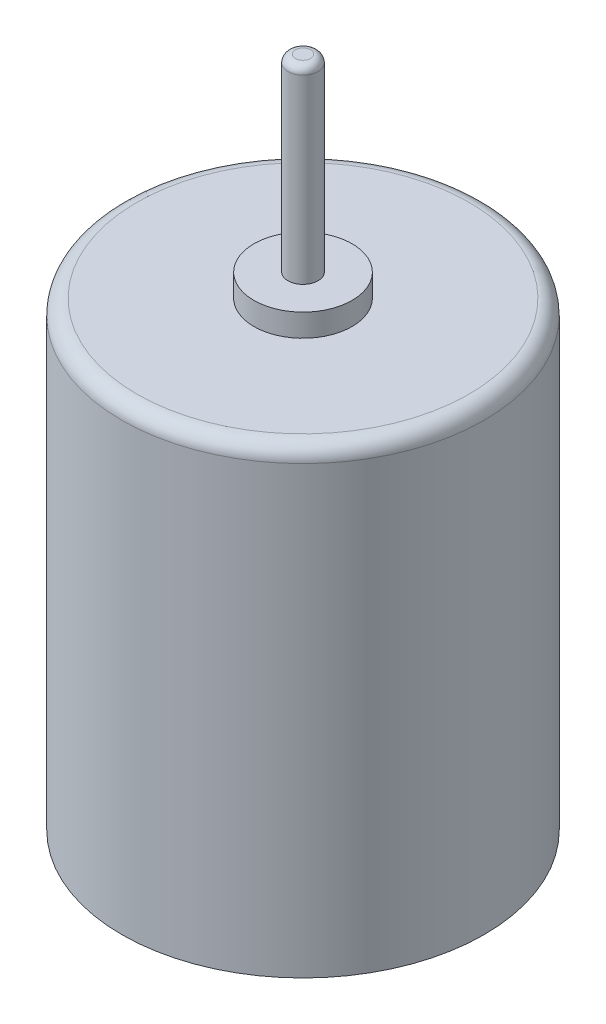
SolidWorks part; units mm, degrees
ref_plane "Front Plane" through (0, 0, 0) normal (0, 0, 1) x (1, 0, 0)
ref_plane "Top Plane" through (0, 0, 0) normal (0, 1, 0) x (1, 0, 0)
ref_plane "Right Plane" through (0, 0, 0) normal (1, 0, 0) x (0, 0, -1)
sketch "Sketch1" plane through (0, 0, 0) normal (0, 1, 0) x (1, 0, 0)
  circle A0 centre (-13.1051, 2.5029) radius 12
  circle A1 centre (-13.1051, 2.5029) radius 3.25
  circle A2 centre (-13.1051, 2.5029) radius 1
  dimension "D1" = 24
  dimension "D2" = 6.5
  dimension "D3" = 2
extrude "Boss-Extrude1" add sketch "Sketch1" along normal blind 30.5 contours A0
extrude "Boss-Extrude2" add sketch "Sketch1<3>" along normal blind 32 contours A1 A2 region at (-16.2632, 0, -2.5029)
sketch "Sketch1<3>" plane through (0, 0, 0) normal (0, 1, 0) x (1, 0, 0) same geometry as "Sketch1"
extrude "Boss-Extrude3" add sketch "Sketch1<4>" along normal blind 44.5 contours A2
sketch "Sketch1<4>" plane through (0, 0, 0) normal (0, 1, 0) x (1, 0, 0) same geometry as "Sketch1"
fillet "Fillet1" radius 0.5 1 edges at (-13.1051, 44.5, -1.5029)
fillet "Fillet2" radius 1 1 edges at (-13.1051, 30.5, 9.4971)
